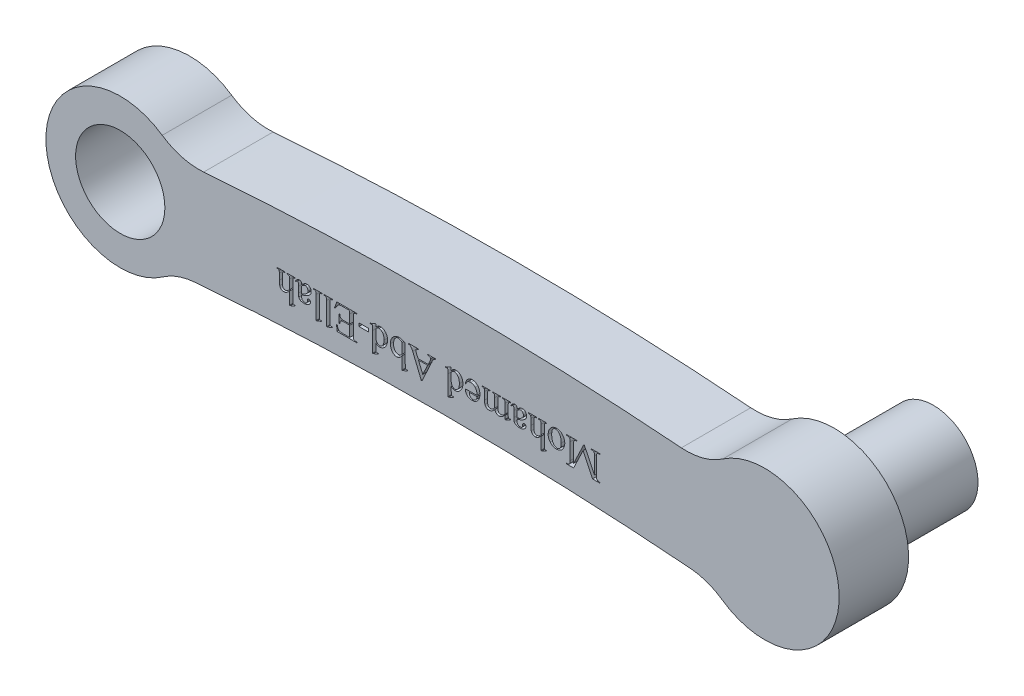
SolidWorks part; units mm, degrees
material "Cast Alloy Steel"
ref_plane "Front Plane" through (0, 0, 0) normal (0, 0, 1) x (1, 0, 0)
ref_plane "Top Plane" through (0, 0, 0) normal (0, 1, 0) x (1, 0, 0)
ref_plane "Right Plane" through (0, 0, 0) normal (1, 0, 0) x (0, 0, -1)
sketch "Sketch1" plane through (0, 0, 0) normal (0, 0, 1) x (1, 0, 0)
  line L0 (0, 0) -> (-500, 0)
  line L1 (-500, 60) -> (0, 60) construction
  line L2 (0, 50) -> (0, -50) construction
  line L3 (-500, 50) -> (-500, -50) construction
  circle A0 centre (75, 0) radius 75
  circle A1 centre (-575, 0) radius 75
  arc A2 (-500, 50) -> (0, 50) centre (-250, -3070) cw
  arc A3 (-500, -50) -> (0, -50) centre (-250, -3170) cw
  arc A4 (-532.6648, 61.909) -> (-462.0088, 60) centre (-495.8567, 115.7355) ccw
  arc A5 (-500, -50) -> (-532.0951, -61.5156) centre (-494.7917, -115) ccw
  arc A6 (-37.9912, 60) -> (32.6648, 61.909) centre (-4.1433, 115.7355) ccw
  arc A7 (32.0951, -61.5156) -> (0, -50) centre (-5.2083, -115) ccw
  circle A8 centre (75, 0) radius 45
  circle A9 centre (-575, 0) radius 45
  dimension "D2" = 50
  dimension "D5" = 150
  dimension "D7" = 90
  dimension "D8" = 90
  dimension "D1" = 500
  dimension "D3" = 50
  dimension "D4" = 60
  dimension "D6" = 50
extrude "Boss-Extrude1" add sketch "Sketch1" along normal blind 70 contours A0 A8 | A6 A2 A4 A1 L0 A0 | A7 A0 L0 A1 A5 A3 | A1 A9 region at (-250, -22.3435, 0) region at (-250, 28.7171, 0) region at (10.5432, 34.0091, 0) region at (-510.3869, -33.7112, 0)
sketch "Sketch2" plane through (0, 0, 0) normal (0, 0, -1) x (-1, 0, 0)
  circle A0 centre (-75, 0) radius 45 construction
  circle A1 centre (-75, 0) radius 45
extrude "Boss-Extrude2" add sketch "Sketch2" along normal blind 100
extrude "Boss-Extrude3" add sketch "Sketch2<2>" against normal up to surface (70 mm away) up to face at (-250, 2.1933, 70)
sketch "Sketch2<2>" plane through (0, 0, 0) normal (0, 0, -1) x (-1, 0, 0) same geometry as "Sketch2"
sketch "Sketch3" plane through (0, 0, 70) normal (0, 0, 1) x (1, 0, 0)
  line L0 (0, 4.4643) -> (-508.1189, 4.4643) construction
  text T0 "Mohamed Abd-Ellah" font "Times New Roman" height in points 100
extrude "Cut-Extrude1" cut sketch "Sketch3" against normal blind 10
